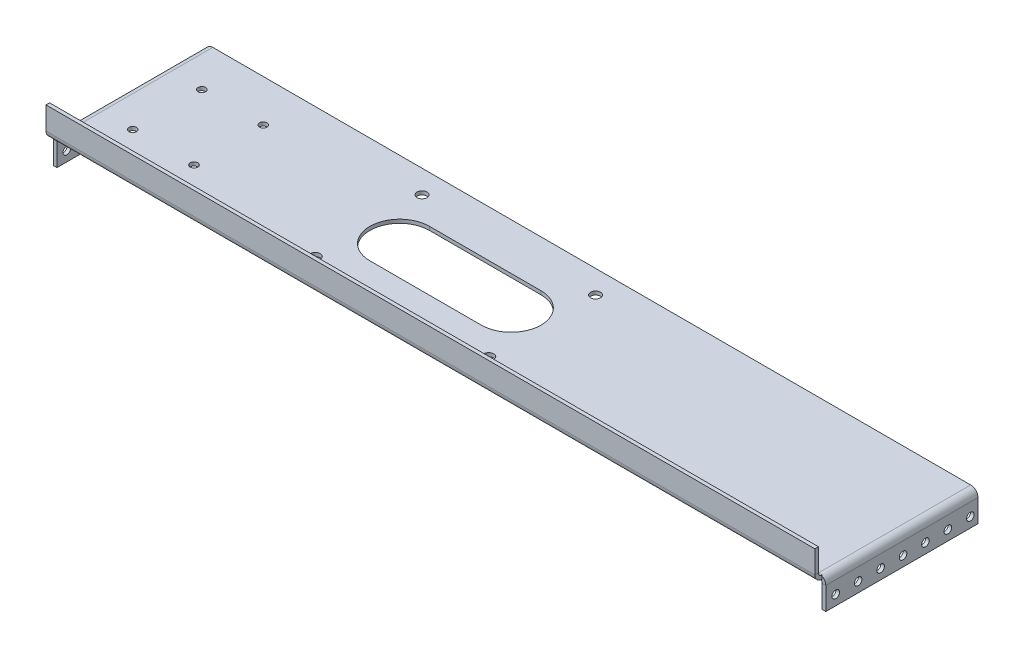
SolidWorks part; units mm, degrees
note: The reader was unsure of these and kept them because the rebuilt part matched: thickness of "Base-Flange1", "Edge-Flange1", "Edge-Flange2", "Edge-Flange3", "Sheet-Metal1", "Sheet-Metal2", "Sheet-Metal3", "Sheet-Metal4", "Sheet-Metal5", "Sheet-Metal13", "Sheet-Metal18", "Sheet-Metal19"; flange length of "Edge-Flange1", "Edge-Flange2", "Edge-Flange3".
ref_plane "Front Plane" through (0, 0, 0) normal (0, 0, 1) x (1, 0, 0)
ref_plane "Top Plane" through (0, 0, 0) normal (0, 1, 0) x (1, 0, 0)
ref_plane "Right Plane" through (0, 0, 0) normal (1, 0, 0) x (0, 0, -1)
sketch "Sketch1" plane through (0, 0, 0) normal (0, 1, 0) x (1, 0, 0)
  line L1 (244.844, -88.9) -> (-244.844, -88.9)
  line L2 (244.844, -88.9) -> (244.844, 88.9)
  line L3 (244.844, 88.9) -> (-244.844, 88.9)
  line L4 (-244.844, -88.9) -> (-244.844, 88.9)
  line L5 (244.844, -88.9) -> (-244.844, 88.9) construction
  line L6 (244.844, 88.9) -> (-244.844, -88.9) construction
  point P0 (0, 0)
  dimension "D1" = 489.688
  dimension "D2" = 177.8
base flange "Base-Flange1" sketch "Sketch1" thickness 2.286 reverse thickness direction no parameters "D1"=0.8128
edge flange "Edge-Flange1" sketch "Sketch8" flange angle 90 flange length 19.05 flange position material inside bend radius 2.36 thickness 2.286 relief rectangular parameters "D6"=10
sketch "Sketch8" plane through (0, 0, 88.9) normal (0, 0, 1) x (1, 0, 0)
  line L2 (-244.844, 0) -> (-244.844, 16.764)
  line L3 (-244.844, 16.764) -> (244.844, 16.764)
  line L4 (244.844, 16.764) -> (244.844, 0)
  line L11 (-244.844, 0) -> (244.844, 0) construction
  line L12 (-244.844, 0) -> (244.844, 0)
bend "EdgeBend1" bend radius 2.36 bend angle 90 parameters "D5"=1
edge flange "Edge-Flange2" sketch "Sketch11" flange angle 90 flange length 19.05 flange position material inside bend radius 2.36 thickness 2.286 relief none parameters "D6"=10
sketch "Sketch11" plane through (-244.844, -2.286, 0) normal (-1, 0, 0) x (0, 0, -1)
  line L0 (88.9, 0) -> (-84.254, 0) construction
  line L1 (88.9, 0) -> (-84.254, 0)
  line L2 (-84.254, 0) -> (-84.254, 16.764)
  line L3 (-84.254, 16.764) -> (88.9, 16.764)
  line L4 (88.9, 16.764) -> (88.9, 0)
bend "EdgeBend2" bend radius 2.36 bend angle 90 parameters "D5"=2
edge flange "Edge-Flange3" sketch "Sketch14" flange angle 90 flange length 19.05 flange position material outside bend radius 2.36 thickness 2.286 relief none parameters "D6"=10
sketch "Sketch14" plane through (244.844, -2.286, 0) normal (1, 0, 0) x (0, 0, 1)
  line L2 (-88.9, 0) -> (-88.9, 16.764)
  line L3 (-88.9, 16.764) -> (84.254, 16.764)
  line L4 (84.254, 16.764) -> (84.254, 0)
  line L7 (84.254, 0) -> (-88.9, 0) construction
  line L8 (84.254, 0) -> (-88.9, 0)
bend "EdgeBend3" bend radius 2.36 bend angle 90 parameters "D5"=3
sketch "Sketch15" plane through (0, 0, 0) normal (0, 1, 0) x (1, 0, 0)
  line L0 (242.484, -84.254) -> (-240.198, -84.254) construction
  line L5 (-92.248, -69.994) -> (18.252, -69.994) construction
  line L13 (-92.248, -69.994) -> (-92.248, -1.994) construction
  line L14 (-92.248, -1.994) -> (18.252, -1.994) construction
  line L15 (18.252, -69.994) -> (18.252, -1.994) construction
  line L16 (-92.248, -69.994) -> (18.252, -1.994) construction
  line L17 (-92.248, -1.994) -> (18.252, -69.994) construction
  line L18 (-1.498, -54.994) -> (-72.498, -54.994)
  line L20 (-1.498, -16.994) -> (-72.498, -16.994)
  line L22 (-1.498, -54.994) -> (-72.498, -16.994) construction
  line L23 (-1.498, -16.994) -> (-72.498, -54.994) construction
  line L24 (-240.198, 88.9) -> (-240.198, -84.254) construction
  circle A8 centre (-92.248, -1.994) radius 3.15
  circle A9 centre (-92.248, -69.994) radius 3.15
  circle A10 centre (18.252, -69.994) radius 3.15
  circle A11 centre (18.252, -1.994) radius 3.15
  arc A12 (-72.498, -16.994) -> (-72.498, -54.994) centre (-72.498, -35.994) ccw
  arc A13 (-1.498, -16.994) -> (-1.498, -54.994) centre (-1.498, -35.994) cw
  point P0 (-36.998, -35.994)
  point P9 (-36.998, -35.994)
  dimension "D3" = 6.3
  dimension "D6" = 18.6055
  dimension "D7" = 19
  dimension "D8" = 19
  dimension "D1" = 110.5
  dimension "D2" = 68
  dimension "D4" = 38
  dimension "D5" = 71
  dimension "D9" = 48.26
  dimension "D10" = 203.2
extrude "Cut-Extrude1" cut sketch "Sketch15" against normal blind 6.35 normal cut yes
sketch "Sketch33" plane through (0, 0, 0) normal (0, 1, 0) x (1, 0, 0)
  line L0 (242.484, 88.9) -> (-240.198, 88.9) construction
  line L1 (247.13, 12.7) -> (-244.844, 12.7)
  line L2 (247.13, 12.7) -> (247.13, 165.1)
  line L3 (247.13, 165.1) -> (-244.844, 165.1)
  line L4 (-244.844, 12.7) -> (-244.844, 165.1)
  line L5 (247.13, 12.7) -> (-244.844, 165.1) construction
  line L6 (247.13, 165.1) -> (-244.844, 12.7) construction
  line L7 (-244.844, 88.9) -> (-244.844, -84.254) construction
  line L8 (244.844, -88.9) -> (-244.844, -88.9) construction
  point P0 (1.143, 88.9)
  dimension "D1" = 101.6
extrude "Cut-Extrude5" cut sketch "Sketch33" against normal through all normal cut yes
sketch "Sketch38" plane through (0, -2.286, 0) normal (0, -1, 0) x (1, 0, 0)
  line L0 (-240.198, -12.7) -> (-240.198, 84.254) construction
  line L1 (-136.398, 42.25) -> (-115.398, 42.25) construction
  line L2 (-136.398, 42.25) -> (-136.398, 21.25) construction
  line L3 (-136.398, 21.25) -> (-115.398, 21.25) construction
  line L4 (-115.398, 42.25) -> (-115.398, 21.25) construction
  line L5 (-136.398, 42.25) -> (-115.398, 21.25) construction
  line L6 (-136.398, 21.25) -> (-115.398, 42.25) construction
  line L7 (-240.198, -12.7) -> (242.484, -12.7) construction
  line L8 (-218.948, 42.25) -> (-197.948, 42.25) construction
  line L9 (-218.948, 42.25) -> (-218.948, 21.25) construction
  line L10 (-218.948, 21.25) -> (-197.948, 21.25) construction
  line L11 (-197.948, 42.25) -> (-197.948, 21.25) construction
  line L12 (-218.948, 42.25) -> (-197.948, 21.25) construction
  line L13 (-218.948, 21.25) -> (-197.948, 42.25) construction
  circle A0 centre (-115.398, 42.25) radius 2.25
  circle A1 centre (-115.398, 21.25) radius 2.25
  circle A2 centre (-136.398, 42.25) radius 2.25
  circle A3 centre (-136.398, 21.25) radius 2.25
  circle A4 centre (-125.898, 31.75) radius 9.1
  circle A5 centre (-197.948, 42.25) radius 2.25
  circle A6 centre (-197.948, 21.25) radius 2.25
  circle A7 centre (-218.948, 42.25) radius 2.25
  circle A8 centre (-218.948, 21.25) radius 2.25
  circle A9 centre (-208.448, 31.75) radius 9.1
  point P0 (-125.898, 31.75)
  point P16 (-208.448, 31.75)
  dimension "D3" = 4.5
  dimension "D6" = 18.2
  dimension "D8" = 4.5
  dimension "D9" = 18.2
  dimension "D1" = 21
  dimension "D2" = 21
  dimension "D4" = 114.3
  dimension "D5" = 44.45
  dimension "D7" = 21
  dimension "D10" = 31.75
sketch "Sketch40" plane through (-244.844, 0, 0) normal (-1, 0, 0) x (0, 0, 1)
  line L0 (84.254, -19.05) -> (84.254, -4.646) construction
  line L1 (-12.7, -19.05) -> (84.254, -19.05) construction
  circle A0 centre (77.904, -12.7) radius 2.413
  circle A1 centre (63.6165, -12.7) radius 2.413
  circle A2 centre (49.329, -12.7) radius 2.413
  circle A3 centre (35.0415, -12.7) radius 2.413
  circle A4 centre (20.754, -12.7) radius 2.413
  circle A5 centre (6.4665, -12.7) radius 2.413
  circle A6 centre (-7.821, -12.7) radius 2.413
  dimension "D1" = 4.826
  dimension "D3" = 14.2875
  dimension "D4" = 6.35
  dimension "D5" = 6.35
  dimension "D2" = 7
extrude "Cut-Extrude10" cut sketch "Sketch40" against normal through all normal cut yes
ref_plane "Plane1" through (-1.498, 0, 0) normal (-1, 0, 0) x (0, 0, 1)
ref_plane "Plane2" through (-72.498, 0, 0) normal (-1, 0, 0) x (0, 0, 1)
sketch "Sketch41" plane through (0, 0, 0) normal (0, 1, 0) x (1, 0, 0)
  line L0 (-1.498, -16.994) -> (-72.498, -16.994) construction
  point P0 (-36.998, -16.994)
sketch "Sketch42" plane through (0, 0, 0) normal (0, 1, 0) x (1, 0, 0)
  line L1 (-181.3694, -58.1085) -> (-220.4194, -58.1085) construction
  line L2 (-181.3694, -58.1085) -> (-181.3694, -14.0585) construction
  line L3 (-181.3694, -14.0585) -> (-220.4194, -14.0585) construction
  line L4 (-220.4194, -58.1085) -> (-220.4194, -14.0585) construction
  line L5 (-181.3694, -58.1085) -> (-220.4194, -14.0585) construction
  line L6 (-181.3694, -14.0585) -> (-220.4194, -58.1085) construction
  circle A0 centre (-220.4194, -14.0585) radius 2.4
  circle A1 centre (-181.3694, -14.0585) radius 2.4
  circle A2 centre (-181.3694, -58.1085) radius 2.4
  circle A3 centre (-220.4194, -58.1085) radius 2.4
  point P0 (-200.8944, -36.0835)
  point P9 (-207.5893, -34.649)
  point P10 (-200.8944, -36.0835)
  dimension "D3" = 4.8
  dimension "D1" = 39.05
  dimension "D2" = 44.05
extrude "Cut-Extrude11" cut sketch "Sketch42" against normal through all normal cut yes
sketch "Bend-Lines1" [suppressed] plane through (0, 0, 0) normal (0, 1, 0) x (1, 0, 0)
sketch "Bounding-Box1" [suppressed] plane through (0, 0, 0) normal (0, 1, 0) x (1, 0, 0)
sheet metal parameters "Sheet-Metal1" thickness 2.286 parameters "D1"=10, "D7"=2.3622
flat pattern "Flat-Pattern1" [suppressed]
sketch "Bend-Lines2" plane through (0, 0, 0) normal (0, 1, 0) x (1, 0, 0)
sketch3d "Bounding-Box2" [suppressed]
  line L0 (-255.27, -88.9, 0) -> (255.27, -88.9, 0) construction
  line L1 (-255.27, 88.9, 0) -> (255.27, 88.9, 0) construction
  line L2 (-255.27, -88.9, 0) -> (-255.27, 88.9, 0) construction
  line L3 (255.27, -88.9, 0) -> (255.27, 88.9, 0) construction
sheet metal parameters "Sheet-Metal2" thickness 2.286 parameters "D1"=10, "D7"=2.3622
flat pattern "Flat-Pattern1"
sketch "Bend-Lines2" plane through (0, 0, 0) normal (0, 1, 0) x (1, 0, 0)
  line L0 (-255.27, -86.959) -> (255.27, -86.959) construction
  line L1 (-255.27, -86.959) -> (255.27, -86.959) construction
sketch3d "Bounding-Box2" [suppressed]
  line L0 (255.27, -104.0679, 0) -> (-255.27, -104.0679, 0) construction
  line L1 (255.27, 88.9, 0) -> (-255.27, 88.9, 0) construction
  line L2 (255.27, -104.0679, 0) -> (255.27, 88.9, 0) construction
  line L3 (-255.27, -104.0679, 0) -> (-255.27, 88.9, 0) construction
bend of the flat pattern "Flatten-<EdgeBend1>1"
sheet metal parameters "Sheet-Metal3" thickness 2.286 parameters "D1"=10, "D7"=2.3622
flat pattern "Flat-Pattern1" [suppressed]
sketch "Bend-Lines2" plane through (0, 0, 0) normal (0, 1, 0) x (1, 0, 0)
  line L0 (-255.27, -86.959) -> (255.27, -86.959) construction
  line L1 (-255.27, -86.959) -> (255.27, -86.959) construction
  line L2 (-253.329, 88.9) -> (-253.329, -84.1778) construction
  line L3 (-253.329, 88.9) -> (-253.329, -84.1778) construction
sketch3d "Bounding-Box2" [suppressed]
  line L0 (255.27, -104.0679, 0) -> (-270.4379, -104.0679, 0) construction
  line L1 (255.27, 88.9, 0) -> (-270.4379, 88.9, 0) construction
  line L2 (255.27, -104.0679, 0) -> (255.27, 88.9, 0) construction
  line L3 (-270.4379, -104.0679, 0) -> (-270.4379, 88.9, 0) construction
bend of the flat pattern "Flatten-<EdgeBend1>1"
bend of the flat pattern "Flatten-<EdgeBend2>1"
sheet metal parameters "Sheet-Metal4" thickness 2.286 parameters "D1"=10, "D7"=2.3622
flat pattern "Flat-Pattern1" [suppressed]
sketch "Bend-Lines2" plane through (0, 0, 0) normal (0, 1, 0) x (1, 0, 0)
  line L0 (-244.844, -86.959) -> (244.844, -86.959) construction
  line L1 (-244.844, -86.959) -> (244.844, -86.959) construction
  line L2 (-242.903, 88.9) -> (-242.903, -84.1778) construction
  line L3 (-242.903, 88.9) -> (-242.903, -84.1778) construction
  line L4 (245.2652, -84.1778) -> (245.2652, 88.9) construction
  line L5 (245.2652, -84.1778) -> (245.2652, 88.9) construction
sketch3d "Bounding-Box2" [suppressed]
  line L0 (262.3741, -104.0679, 0) -> (-260.0119, -104.0679, 0) construction
  line L1 (262.3741, 88.9, 0) -> (-260.0119, 88.9, 0) construction
  line L2 (262.3741, -104.0679, 0) -> (262.3741, 88.9, 0) construction
  line L3 (-260.0119, -104.0679, 0) -> (-260.0119, 88.9, 0) construction
bend of the flat pattern "Flatten-<EdgeBend3>1"
bend of the flat pattern "Flatten-<EdgeBend1>1"
bend of the flat pattern "Flatten-<EdgeBend2>1"
sheet metal parameters "Sheet-Metal5" thickness 2.286 parameters "D1"=10, "D7"=2.3622
flat pattern "Flat-Pattern1" [suppressed]
sketch "Bend-Lines2" plane through (0, 0, 0) normal (0, 1, 0) x (1, 0, 0)
  line L0 (-244.844, -86.959) -> (244.844, -86.959) construction
  line L1 (-244.844, -86.959) -> (244.844, -86.959) construction
  line L2 (-242.903, 88.9) -> (-242.903, -84.1778) construction
  line L3 (-242.903, 88.9) -> (-242.903, -84.1778) construction
  line L4 (245.2652, -84.1778) -> (245.2652, 88.9) construction
  line L5 (245.2652, -84.1778) -> (245.2652, 88.9) construction
sketch3d "Bounding-Box2" [suppressed]
  line L0 (262.3741, -104.0679, 0) -> (-260.0119, -104.0679, 0) construction
  line L1 (262.3741, 88.9, 0) -> (-260.0119, 88.9, 0) construction
  line L2 (262.3741, -104.0679, 0) -> (262.3741, 88.9, 0) construction
  line L3 (-260.0119, -104.0679, 0) -> (-260.0119, 88.9, 0) construction
bend of the flat pattern "Flatten-<EdgeBend1>1"
bend of the flat pattern "Flatten-<EdgeBend3>1"
bend of the flat pattern "Flatten-<EdgeBend2>1"
sheet metal parameters "Sheet-Metal13" thickness 2.286 parameters "D1"=10, "D7"=2.3622
flat pattern "Flat-Pattern1" [suppressed]
sketch "Bend-Lines2" plane through (0, 0, 0) normal (0, 1, 0) x (1, 0, 0)
  line L0 (245.2652, -84.1778) -> (245.2652, 69.85) construction
  line L1 (-242.903, 69.85) -> (-242.903, -84.1778) construction
  line L2 (-244.844, -86.959) -> (244.844, -86.959) construction
  line L3 (245.2652, -84.1778) -> (245.2652, 69.85) construction
  line L4 (-242.903, 69.85) -> (-242.903, -84.1778) construction
  line L5 (-244.844, -86.959) -> (244.844, -86.959) construction
sketch3d "Bounding-Box2" [suppressed]
  line L0 (262.3741, -104.0679, 0) -> (-260.0119, -104.0679, 0) construction
  line L1 (262.3741, 69.85, 0) -> (-260.0119, 69.85, 0) construction
  line L2 (262.3741, -104.0679, 0) -> (262.3741, 69.85, 0) construction
  line L3 (-260.0119, -104.0679, 0) -> (-260.0119, 69.85, 0) construction
bend of the flat pattern "Flatten-<EdgeBend3>2"
bend of the flat pattern "Flatten-<EdgeBend1>2"
bend of the flat pattern "Flatten-<EdgeBend2>2"
sheet metal parameters "Sheet-Metal18" thickness 2.286 parameters "D1"=10, "D7"=2.3622
flat pattern "Flat-Pattern1"
sketch "Bend-Lines2" plane through (0, 0, 0) normal (0, 1, 0) x (1, 0, 0)
  line L0 (245.0018, -84.254) -> (245.0018, 12.7) construction
  line L1 (-242.7158, 12.7) -> (-242.7158, -84.254) construction
  line L2 (-244.844, -86.7718) -> (244.844, -86.7718) construction
  line L3 (245.0018, -84.254) -> (245.0018, 12.7) construction
  line L4 (-242.7158, 12.7) -> (-242.7158, -84.254) construction
  line L5 (-244.844, -86.7718) -> (244.844, -86.7718) construction
sketch3d "Bounding-Box2" [suppressed]
  line L0 (261.9237, -103.6937, 0) -> (-259.6377, -103.6937, 0) construction
  line L1 (261.9237, 12.7, 0) -> (-259.6377, 12.7, 0) construction
  line L2 (261.9237, -103.6937, 0) -> (261.9237, 12.7, 0) construction
  line L3 (-259.6377, -103.6937, 0) -> (-259.6377, 12.7, 0) construction
bend of the flat pattern "Flatten-<EdgeBend3>2"
bend of the flat pattern "Flatten-<EdgeBend1>2"
bend of the flat pattern "Flatten-<EdgeBend2>2"
sheet metal parameters "Sheet-Metal19" thickness 2.286 parameters "D1"=10, "D7"=2.3622
flat pattern "Flat-Pattern1"
sketch "Bend-Lines2" plane through (0, 0, 0) normal (0, 1, 0) x (1, 0, 0)
  line L0 (245.0018, -84.254) -> (245.0018, 12.7) construction
  line L1 (-242.7158, 12.7) -> (-242.7158, -84.254) construction
  line L2 (-244.844, -86.7718) -> (244.844, -86.7718) construction
  line L3 (245.0018, -84.254) -> (245.0018, 12.7) construction
  line L4 (-242.7158, 12.7) -> (-242.7158, -84.254) construction
  line L5 (-244.844, -86.7718) -> (244.844, -86.7718) construction
sketch3d "Bounding-Box2" [suppressed]
  line L0 (261.9237, -103.6937, 0) -> (-259.6377, -103.6937, 0) construction
  line L1 (261.9237, 12.7, 0) -> (-259.6377, 12.7, 0) construction
  line L2 (261.9237, -103.6937, 0) -> (261.9237, 12.7, 0) construction
  line L3 (-259.6377, -103.6937, 0) -> (-259.6377, 12.7, 0) construction
bend of the flat pattern "Flatten-<EdgeBend3>2"
bend of the flat pattern "Flatten-<EdgeBend1>2"
bend of the flat pattern "Flatten-<EdgeBend2>2"
